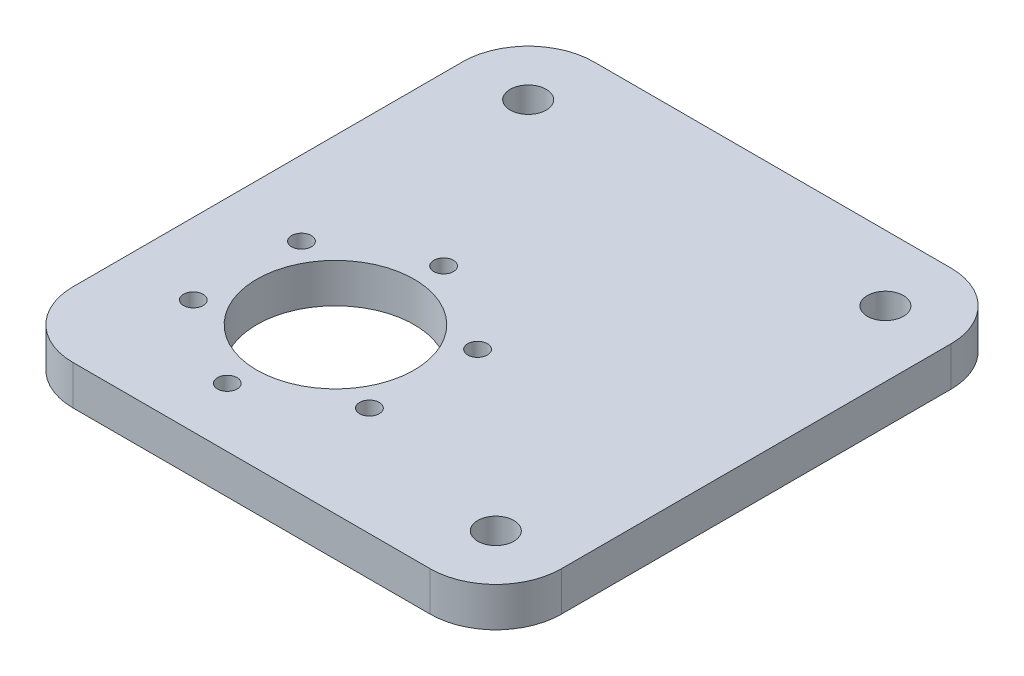
SolidWorks part; units mm, degrees
ref_plane "Front Plane" through (0, 0, 0) normal (0, 0, 1) x (1, 0, 0)
ref_plane "Top Plane" through (0, 0, 0) normal (0, 1, 0) x (1, 0, 0)
ref_plane "Right Plane" through (0, 0, 0) normal (1, 0, 0) x (0, 0, -1)
sketch "Sketch2" plane through (0, 0, 0) normal (0, 1, 0) x (1, 0, 0)
  line L1 (-18.6933, 53.5256) -> (55.7467, 53.5256)
  line L2 (-18.6933, 53.5256) -> (-18.6933, -25.8544)
  line L3 (-18.6933, -25.8544) -> (55.7467, -25.8544)
  line L4 (55.7467, 53.5256) -> (55.7467, -25.8544)
  circle A0 centre (6.3067, -0.8544) radius 12
  dimension "D1" = 24
  dimension "D2" = 74.44
  dimension "D3" = 79.38
extrude "Boss-Extrude1" add sketch "Sketch2" along normal blind 6
sketch "Sketch6" plane through (0, 0, 0) normal (0, -1, 0) x (1, 0, 0)
  line L0 (55.7467, 25.8544) -> (55.7467, -53.5256) construction
  line L1 (55.7467, -53.5256) -> (-18.6933, -53.5256) construction
  line L2 (-18.6933, 25.8544) -> (55.7467, 25.8544) construction
  line L3 (-18.6933, -53.5256) -> (-18.6933, 25.8544) construction
  circle A0 centre (45.7467, 15.8544) radius 2.75
  circle A2 centre (45.7467, -43.5256) radius 2.75
  circle A3 centre (-8.6933, -43.5256) radius 2.75
  dimension "D5" = 5.5
  dimension "D6" = 5.5
  dimension "D7" = 5.5
  dimension "D1" = 10
  dimension "D2" = 10
  dimension "D3" = 10
  dimension "D4" = 10
extrude "Cut-Extrude2" cut sketch "Sketch6" against normal blind 10
sketch "Sketch7" plane through (0, 0, 0) normal (0, -1, 0) x (1, 0, 0)
  circle A0 centre (-7.2956, -7.5704) radius 1.25 construction
  circle A1 centre (-7.2956, -7.5704) radius 1.25
  circle A2 centre (-7.7905, 8.422) radius 1.25 construction
  circle A3 centre (-7.7905, 8.422) radius 1.25
  circle A4 centre (19.9091, 9.2791) radius 1.25 construction
  circle A5 centre (19.9091, 9.2791) radius 1.25
  circle A6 centre (20.4039, -6.7133) radius 1.25 construction
  circle A7 centre (20.4039, -6.7133) radius 1.25
  circle A8 centre (5.8119, 16.8467) radius 1.25 construction
  circle A9 centre (5.8119, 16.8467) radius 1.25
  circle A10 centre (6.8016, -15.138) radius 1.25 construction
  circle A11 centre (6.8016, -15.138) radius 1.25
sketch "Sketch8" plane through (0, 0, 0) normal (0, -1, 0) x (1, 0, 0)
  circle A0 centre (5.8119, 16.8467) radius 1.5
  circle A1 centre (19.9091, 9.2791) radius 1.5
  circle A2 centre (20.4039, -6.7133) radius 1.5
  circle A3 centre (6.8016, -15.138) radius 1.5
  circle A4 centre (-7.2956, -7.5704) radius 1.5
  circle A5 centre (-7.7905, 8.422) radius 1.5
  dimension "D1" = 3
  dimension "D2" = 3
  dimension "D3" = 3
  dimension "D4" = 3
  dimension "D5" = 3
  dimension "D6" = 3
extrude "Cut-Extrude4" cut sketch "Sketch8" against normal through all
fillet "Fillet1" radius 10 4 edges at (55.7467, 3, -53.5256) (-18.6933, 3, -53.5256) (-18.6933, 3, 25.8544) (55.7467, 3, 25.8544)
